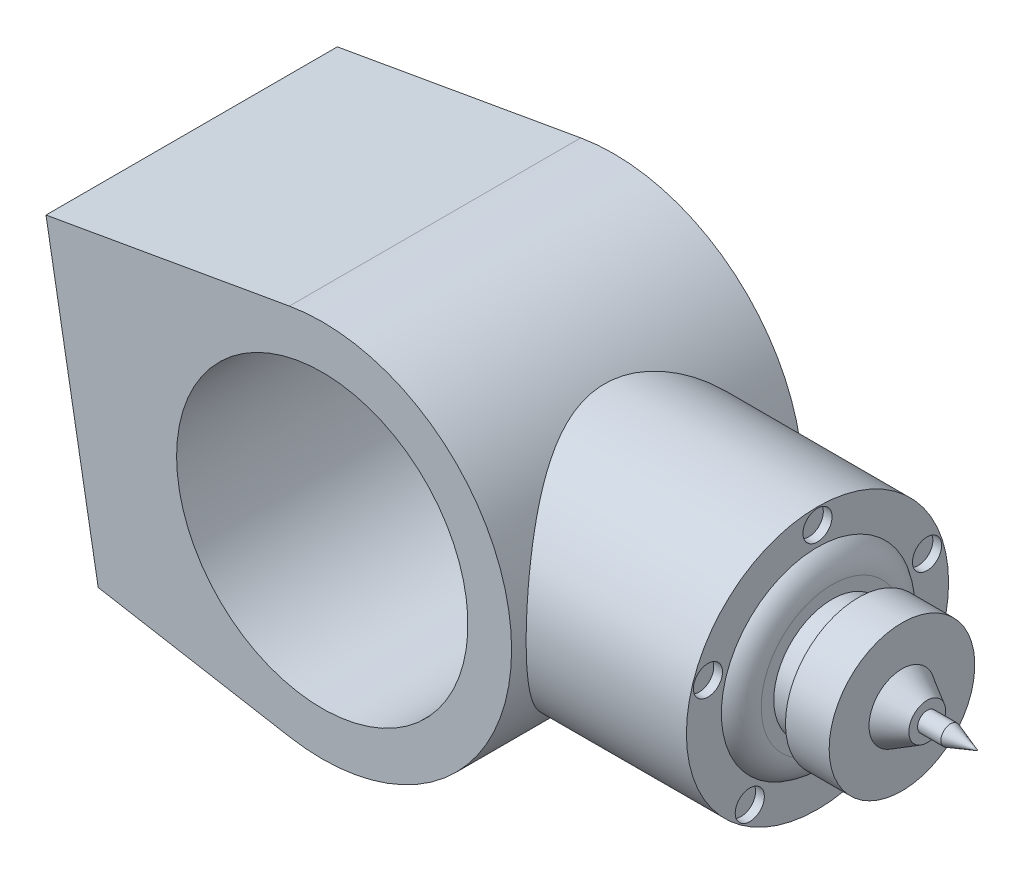
SolidWorks part; units mm, degrees
ref_plane "Front Plane" through (0, 0, 0) normal (0, 0, 1) x (1, 0, 0)
ref_plane "Top Plane" through (0, 0, 0) normal (0, 1, 0) x (1, 0, 0)
ref_plane "Right Plane" through (0, 0, 0) normal (1, 0, 0) x (0, 0, -1)
sketch "Sketch1" plane through (0, 0, 0) normal (0, 0, 1) x (1, 0, 0)
  line L0 (-147.6818, 40) -> (-147.6818, -40)
  line L1 (-147.6818, 40) -> (-11.27, 64.0155)
  line L2 (-147.6818, -40) -> (-11.27, -64.0155)
  arc A0 (-11.27, -64.0155) -> (-11.27, 64.0155) centre (0, 0) ccw
  circle A1 centre (0, 0) radius 50
  point P6 (-147.6818, 0)
  dimension "D1" = 130
  dimension "D3" = 100
  dimension "D2" = 80
extrude "Boss-Extrude1" add sketch "Sketch1" along normal mid plane 100
ref_plane "Plane1" through (120, 0, 0) normal (1, 0, 0) x (0, 0, -1)
sketch "Sketch2" plane through (120, 0, 0) normal (1, 0, 0) x (0, 0, -1)
  circle A0 centre (0, 0) radius 45
  dimension "D1" = 90
extrude "Boss-Extrude2" add sketch "Sketch2" against normal up to next
sketch "Sketch3" plane through (0, 0, 0) normal (0, 0, 1) x (1, 0, 0)
  line L0 (0, 0) -> (219.6158, 0) construction
  line L1 (120, 0) -> (120, -20)
  line L2 (120, -55) -> (120, 55) construction
  line L3 (120, -20) -> (134, -20)
  line L4 (134, -20) -> (134, -25)
  line L5 (134, -25) -> (149, -25)
  line L6 (149, -25) -> (149, -11.3102)
  line L7 (149, -11.3102) -> (157.6603, -6.3102)
  line L8 (157.6603, -6.3102) -> (157.6603, -3.3102)
  line L9 (157.6603, -3.3102) -> (165.6603, -3.3102)
  line L10 (165.6603, -3.3102) -> (175.0965, 0)
  line L11 (175.0965, 0) -> (109.8079, 0)
  dimension "D1" = 10
  dimension "D2" = 8
  dimension "D3" = 120
  dimension "D4" = 15
  dimension "D5" = 10
  dimension "D6" = 14
  dimension "D7" = 20
  dimension "D8" = 5
  dimension "D9" = 3
revolve "Revolve1" add sketch "Sketch3" angle 360 about L0
sketch "Sketch4" plane through (120, 0, 0) normal (1, 0, 0) x (0, 0, -1)
  circle A0 centre (0, 39.543) radius 5
  point P2 (0, 39.543)
  dimension "D1" = 10
extrude "Cut-Extrude4" cut sketch "Sketch4" against normal blind 3
pattern_circular "CirPattern2" count 5 over 360 about axis through (0, 0, 0) along (1, 0, 0) of "Cut-Extrude4"
sketch "Sketch5" plane through (120, 0, 0) normal (1, 0, 0) x (0, 0, -1)
  circle A2 centre (0, 0) radius 33
  circle A3 centre (0, 0) radius 33
  dimension "D1" = 12
extrude "Boss-Extrude3" add sketch "Sketch5" along normal blind 5
fillet "Fillet1" radius 10 1 edges at (125, 0, -33)
sketch "Sketch6" plane through (-147.6818, 0, 0) normal (-1, 0, 0) x (0, 0, 1)
  line L0 (-50, 40) -> (50, 40)
  line L1 (50, 40) -> (50, -40)
  line L2 (50, -40) -> (-50, -40)
  line L3 (-50, -40) -> (-50, 40)
extrude "Cut-Extrude5" cut sketch "Sketch6" against normal blind 37
sketch "Sketch7" plane through (-11.27, 64.0155, 0) normal (-0.1734, 0.9849, 0) x (0.9849, 0.1734, 0)
  line L1 (0, -50) -> (-138.5097, -50) construction
  line L2 (-101.2768, -50) -> (-138.5097, -50)
  line L3 (-138.5097, -50) -> (-138.5097, 50)
  line L4 (-138.5097, 50) -> (-101.2768, 50)
  line L5 (0, 50) -> (-138.5097, 50) construction
  line L6 (-101.2768, 50) -> (-101.2768, -50)
extrude "Cut-Extrude6" cut sketch "Sketch7" against normal blind 8
sketch "Sketch8" plane through (0, -40, 0) normal (0, 1, 0) x (1, 0, 0)
  line L0 (-110.6818, 50) -> (-110.6818, -50)
  line L1 (-110.6818, -50) -> (-147.6818, -50)
  line L2 (-147.6818, -50) -> (-147.6818, 50)
  line L3 (-147.6818, 50) -> (-110.6818, 50)
extrude "Cut-Extrude7" cut sketch "Sketch8" against normal blind 8
sketch "Sketch9" plane through (-11.27, 64.0155, 0) normal (-0.1734, 0.9849, 0) x (0.9849, 0.1734, 0)
  line L0 (-101.2768, 50) -> (-84.8387, 50)
  line L1 (0, 50) -> (-101.2768, 50) construction
  line L2 (-84.8387, 50) -> (-84.8387, -50)
  line L3 (0, -50) -> (-101.2768, -50) construction
  line L4 (-84.8387, -50) -> (-101.2768, -50)
  line L5 (-101.2768, -50) -> (-101.2768, 50) construction
  line L6 (-101.2768, -50) -> (-101.2768, 50)
extrude "Cut-Extrude8" cut sketch "Sketch9" against normal blind 138 from offset 0
sketch "Sketch10" plane through (0, 0, 50) normal (0, 0, 1) x (1, 0, 0)
  line L0 (-104.1016, -35.1791) -> (-110.6818, -46.5139)
  line L1 (-110.6818, -46.5139) -> (-110.6818, 38.3909)
  line L2 (-110.6818, -46.5139) -> (-110.6818, 38.3909) construction
  line L3 (-110.6818, 38.3909) -> (-107.3917, 38.3909)
  line L4 (-107.3917, 38.3909) -> (-90.2372, -50.8053)
  line L5 (-90.2372, -50.8053) -> (-110.6818, -50.8053)
  line L6 (-110.6818, -50.8053) -> (-110.6818, -46.5139)
extrude "Cut-Extrude9" cut sketch "Sketch10" against normal blind 138
sketch "Sketch11" plane through (-9.883, 56.1367, 0) normal (-0.1734, 0.9849, 0) x (0.9849, 0.1734, 0)
  line L0 (-96.0596, -51.9113) -> (-97.9624, 56.7703)
  line L1 (-97.9624, 56.7703) -> (-112.3353, 50)
  line L2 (-112.3353, 50) -> (-108.5176, -51.9113)
  line L3 (-108.5176, -51.9113) -> (-96.0596, -51.9113)
extrude "Cut-Extrude10" cut sketch "Sketch11" against normal blind 138
